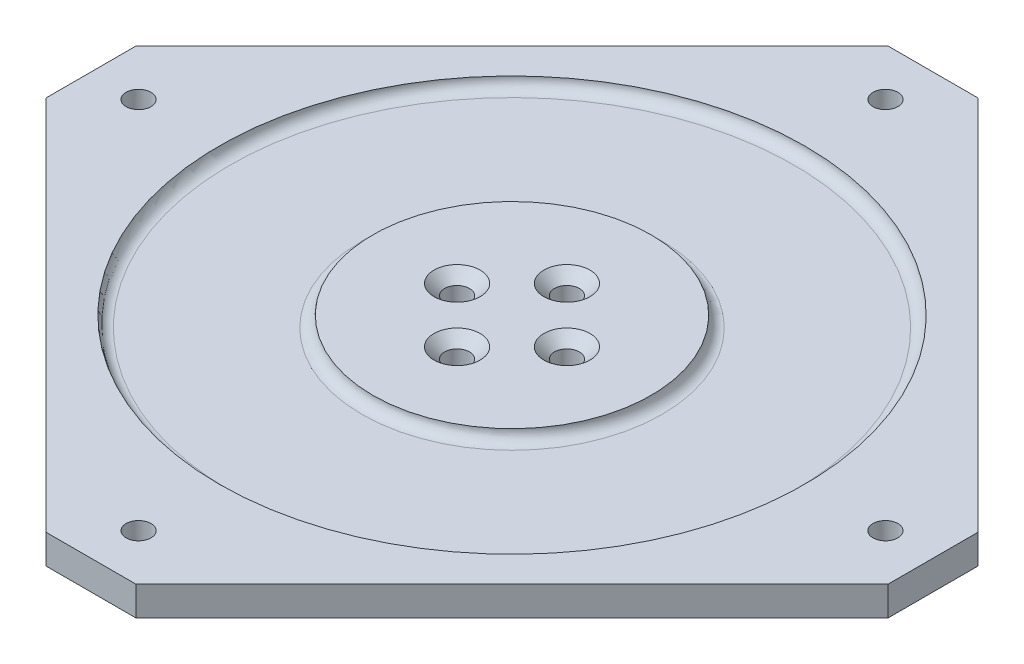
SolidWorks part; units mm, degrees
material "6061-T6 (SS)"
ref_plane "Front Plane" through (0, 0, 0) normal (0, 0, 1) x (1, 0, 0)
ref_plane "Top Plane" through (0, 0, 0) normal (0, 1, 0) x (1, 0, 0)
ref_plane "Right Plane" through (0, 0, 0) normal (1, 0, 0) x (0, 0, -1)
sketch "Sketch1" plane through (0, 0, 0) normal (0, 1, 0) x (1, 0, 0)
  line L0 (-63.6396, 0) -> (0, -63.6396)
  line L1 (-63.6396, 0) -> (0, 63.6396)
  line L2 (0, -63.6396) -> (63.6396, 0)
  line L3 (0, 63.6396) -> (63.6396, 0)
  line L4 (-63.6396, 0) -> (63.6396, 0) construction
  line L5 (0, -63.6396) -> (0, 63.6396) construction
  line L6 (-49.4975, 0) -> (0, 49.4975) construction
  line L7 (0, 49.4975) -> (49.4975, 0) construction
  line L8 (0, -49.4975) -> (49.4975, 0) construction
  line L9 (-49.4975, 0) -> (0, -49.4975) construction
  point P1 (0, 0)
  dimension "D1" = 90
  dimension "D2" = 10
extrude "Mounting base" add sketch "Sketch1" along normal blind 4
sketch "Sketch16" plane through (0, 4, 0) normal (0, 1, 0) x (1, 0, 0)
  line L0 (-7.5, 0) -> (0, -7.5) construction
  line L1 (-7.5, 0) -> (0, 7.5) construction
  line L2 (0, -7.5) -> (7.5, 0) construction
  line L3 (0, 7.5) -> (7.5, 0) construction
  line L4 (-7.5, 0) -> (7.5, 0) construction
  line L5 (0, -7.5) -> (0, 7.5) construction
  point P1 (0, 0)
  point P2 (0, 7.5)
  point P3 (7.5, 0)
  point P9 (0, -7.5)
  point P10 (-7.5, 0)
  dimension "D1" = 15
hole_wizard "CSK for M3 Flat Head Machine Screw2" positions "Sketch21" profile "Sketch20" countersink size "M3" standard "ANSI Metric"
sketch "Sketch21" plane through (0, 0, 0) normal (0, -1, 0) x (-1, 0, 0)
  line L0 (-51, 0) -> (0, 0) construction
  line L1 (0, 0) -> (51, 0) construction
  line L4 (0, 51) -> (0, 0) construction
  line L5 (0, 0) -> (0, -51) construction
  point P0 (51, 0)
  point P2 (0, -51)
  point P4 (-51, 0)
  point P6 (0, 51)
  dimension "D1" = 51
sketch "Sketch20" plane through (-51, 0, 0) normal (1, 0, 0) x (0, 0, -1)
  line L0 (0, 0) -> (0, 5.0215)
  line L1 (0, 5.0215) -> (1.7, 4)
  line L2 (1.7, 4) -> (1.7, 1.45)
  line L3 (1.7, 1.45) -> (3.15, 0)
  line L5 (3.15, 0) -> (0, 0)
  line L6 (-1.7, 1.45) -> (-3.15, 0) construction
  line L10 (0, 5.0215) -> (-1.7, 4) construction
  line L11 (0, -6.35) -> (0, 107.95) construction
  dimension "Hole Dia." = 3.4
  dimension "Hole Depth" = 4
  dimension "Near C'Sink Dia." = 6.3
  dimension "Near C'Sink Angle" = 90
  dimension "Drill Angle" = 118
hole_wizard "CSK for M3 Flat Head Machine Screw1" positions "3DSketch1" profile "Sketch17" countersink size "M3" standard "ANSI Metric" end condition through all
sketch3d "3DSketch1"
  point P0 (0, 4, -7.5)
  point P3 (7.5, 4, 0)
  point P6 (0, 4, 7.5)
  point P9 (-7.5, 4, 0)
sketch "Sketch17" plane through (0, 4, -7.5) normal (1, 0, 0) x (0, 0, 1)
  line L0 (0, 0) -> (0, 4)
  line L1 (0, 4) -> (1.7, 4)
  line L2 (1.7, 4) -> (1.7, 1.45)
  line L3 (1.7, 1.45) -> (3.15, 0)
  line L5 (3.15, 0) -> (0, 0)
  line L6 (-1.7, 1.45) -> (-3.15, 0) construction
  line L11 (0, -6.35) -> (0, 107.95) construction
  dimension "Thru Hole Dia." = 3.4
  dimension "Thru Hole Depth" = 4
  dimension "Near C'Sink Dia." = 6.3
  dimension "Near C'Sink Angle" = 90
sketch "Sketch12" plane through (0, 0, 0) normal (0, 1, 0) x (1, 0, 0)
  line L1 (-57.5, -57.5) -> (57.5, -57.5)
  line L2 (-57.5, -57.5) -> (-57.5, 57.5)
  line L3 (-57.5, 57.5) -> (57.5, 57.5)
  line L4 (57.5, -57.5) -> (57.5, 57.5)
  line L5 (0, 57.5) -> (0, -57.5) construction
  line L6 (-57.5, 0) -> (57.5, 0) construction
  point P0 (0, 0)
  dimension "D1" = 115
  dimension "D2" = 115
extrude "Cut-Extrude2" cut sketch "Sketch12" along normal blind 20 flip side to cut
sketch "Sketch19" plane through (0, 4, 0) normal (0, 1, 0) x (1, 0, 0)
  line L1 (40, 16.5685) -> (16.5685, 40)
  line L2 (16.5685, 40) -> (-16.5685, 40)
  line L3 (-16.5685, 40) -> (-40, 16.5685)
  line L4 (-40, 16.5685) -> (-40, -16.5685)
  line L5 (-40, -16.5685) -> (-16.5685, -40)
  line L6 (-16.5685, -40) -> (16.5685, -40)
  line L7 (16.5685, -40) -> (40, -16.5685)
  line L8 (40, -16.5685) -> (40, 16.5685)
  line L9 (19, 7.8701) -> (7.8701, 19) construction
  line L10 (7.8701, 19) -> (-7.8701, 19) construction
  line L11 (-7.8701, 19) -> (-19, 7.8701) construction
  line L12 (-19, 7.8701) -> (-19, -7.8701) construction
  line L13 (-19, -7.8701) -> (-7.8701, -19) construction
  line L14 (-7.8701, -19) -> (7.8701, -19) construction
  line L15 (7.8701, -19) -> (19, -7.8701) construction
  line L16 (19, -7.8701) -> (19, 7.8701) construction
  circle A0 centre (0, 0) radius 40
  circle A1 centre (0, 0) radius 19
  dimension "D1" = 21
  dimension "D2" = 80
extrude "Cut-Extrude4" cut sketch "Sketch19" against normal blind 1.5 contours A0 A1 region at (35.9099, 4, -14.8744)
extrude "Cut-Extrude5" cut sketch "Sketch19<3>" along normal blind 1.5 from surface contours A0 A1 region at (35.9099, 4, -14.8744) starting at face at (0, 0, 0)
sketch "Sketch19<3>" plane through (0, 4, 0) normal (0, 1, 0) x (1, 0, 0) same geometry as "Sketch19"
fillet "Fillet1" radius 1.5 4 edges at (0, 1.5, -40) (0, 1.5, -19) (0, 2.5, 40) (0, 2.5, 19)
sketch "Sketch9" plane through (0, 0, 0) normal (0, 0, 1) x (1, 0, 0)
  line L0 (0, 0) -> (0, 7.5998) construction
ref_axis "Axis1" through (0, 0, 0) along (0, 1, 0)
sketch "Sketch10" plane through (0, 4, 0) normal (0, 1, 0) x (1, 0, 0)
  line L0 (-2.25, 33.55) -> (2.25, 33.55)
  line L1 (-33.55, -2.25) -> (-26.45, -2.25)
  line L2 (-33.55, -2.25) -> (-33.55, 2.25)
  line L3 (-33.55, 2.25) -> (-26.45, 2.25)
  line L4 (-26.45, -2.25) -> (-26.45, 2.25)
  line L5 (-30, 2.25) -> (-30, -2.25) construction
  line L6 (-33.55, 0) -> (-26.45, 0) construction
  line L7 (2.25, 33.55) -> (2.25, 26.45)
  line L8 (-2.25, 26.45) -> (2.25, 26.45)
  line L9 (-2.25, 33.55) -> (-2.25, 26.45)
  line L10 (2.25, 30) -> (-2.25, 30) construction
  line L11 (0, 33.55) -> (0, 26.45) construction
  line L12 (33.55, 2.25) -> (33.55, -2.25)
  line L13 (33.55, -2.25) -> (26.45, -2.25)
  line L14 (26.45, 2.25) -> (26.45, -2.25)
  line L15 (33.55, 2.25) -> (26.45, 2.25)
  line L16 (30, -2.25) -> (30, 2.25) construction
  line L17 (33.55, 0) -> (26.45, 0) construction
  line L18 (2.25, -33.55) -> (-2.25, -33.55)
  line L19 (-2.25, -33.55) -> (-2.25, -26.45)
  line L20 (2.25, -26.45) -> (-2.25, -26.45)
  line L21 (2.25, -33.55) -> (2.25, -26.45)
  line L22 (-2.25, -30) -> (2.25, -30) construction
  line L23 (0, -33.55) -> (0, -26.45) construction
  line L24 (0, 0) -> (-26.45, 0) construction
  point P14 (0, 30)
  point P21 (30, 0)
  point P30 (0, -30)
  point P136 (-30, 0)
  dimension "D1" = 4.5
  dimension "D2" = 7.1
  dimension "D3" = 30
  dimension "D4" = 4
